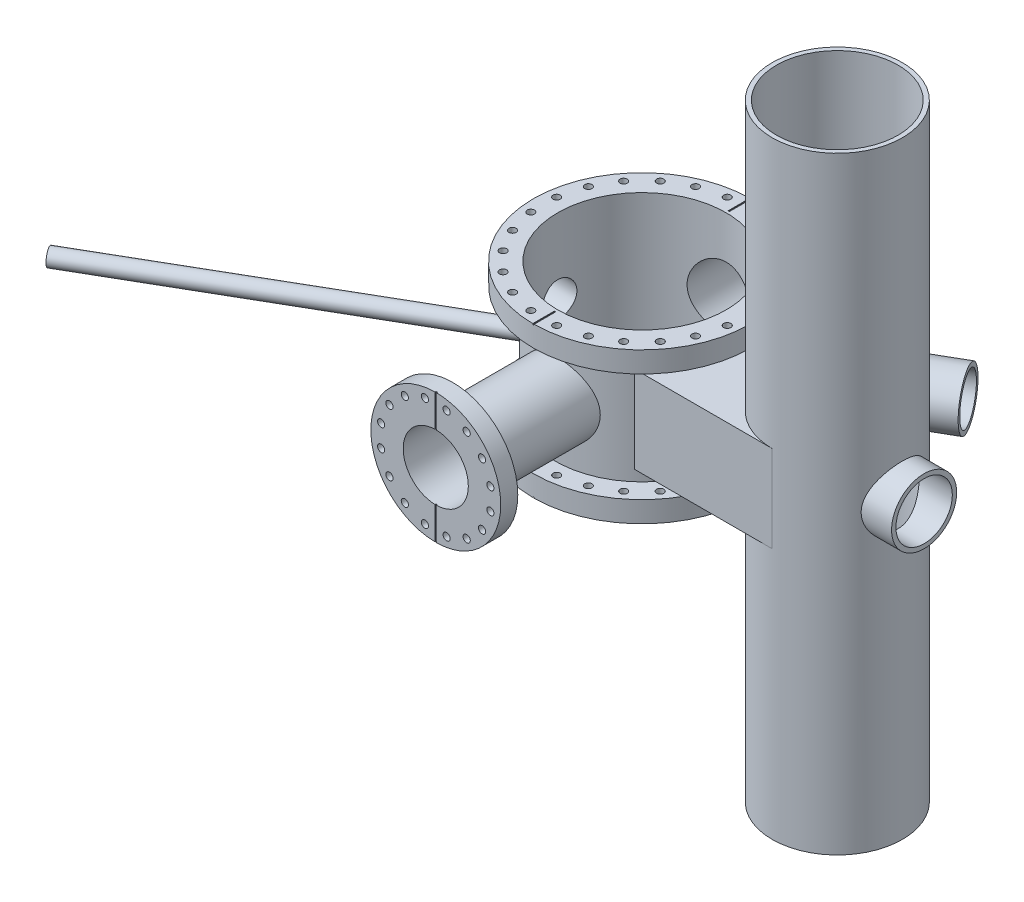
SolidWorks part; units mm, degrees
note: '?' marks a value the reader was unsure of.
ref_plane "Front Plane" through (0, 0, 0) normal (0, 0, 1) x (1, 0, 0)
ref_plane "Top Plane" through (0, 0, 0) normal (0, 1, 0) x (1, 0, 0)
ref_plane "Right Plane" through (0, 0, 0) normal (1, 0, 0) x (0, 0, -1)
sketch "Main_Chamber_Cylinder_Cross_Section" plane through (0, 0, 0) normal (0, 1, 0) x (1, 0, 0)
  circle A0 centre (0, 0) radius 98.552
  circle A1 centre (0, 0) radius 101.6
  dimension "main_chamber_ID_inches" = 197.104
  dimension "main_chamber_wall_thickness_inches" = 3.048
sketch "Main_Chamber_Cylinder_Height" plane through (0, 0, 0) normal (0, 0, 1) x (1, 0, 0)
  line L0 (0, -88.138) -> (0, 88.138) construction
  line L1 (101.6, 0) -> (-101.6, 0) construction
  line L2 (-47.8245, 0) -> (46.1077, 0) construction
  point P8 (0, 0)
  dimension "main_chamber_cyl_height_inches" = 176.276
extrude "Main_Chamber_Cylinder" add sketch "Main_Chamber_Cylinder_Cross_Section" along normal up to vertex (88.138 mm away) and the other way up to vertex (88.138 mm away) up to point (0, 88.138, 0)
sketch "Sketch1" plane through (0, 88.138, 0) normal (0, 1, 0) x (1, 0, 0)
  line L0 (0, 0) -> (0, 125.4308) construction
  point P0 (0, 0)
sketch "Sketch2" plane through (0, -88.138, 0) normal (0, -1, 0) x (1, 0, 0)
  line L0 (0, 0) -> (0, 116.7419) construction
  point P0 (0, 0)
sketch "Sketch21" plane through (0, -88.138, 0) normal (0, -1, 0) x (1, 0, 0)
  circle A0 centre (0, 0) radius 127
  circle A1 centre (0, 0) radius 101.6
  dimension "D1" = 203.2
  dimension "D2" = 254
extrude "Extrude2" add sketch "Sketch21" against normal blind 24.5
sketch "Sketch5" plane through (0, -88.138, 0) normal (0, -1, 0) x (1, 0, 0)
  line L0 (0, 0) -> (0, 210.1139) construction
  line L2 (0, -200000) -> (0, 200116.7419) construction
  line L3 (0, 0) -> (-224.4949, 0) construction
  line L4 (0.7938, 152.45) -> (-0.7938, 152.45)
  line L5 (-0.7938, 152.45) -> (-0.7937, 101.65)
  line L6 (-0.7937, 101.65) -> (0.7937, 101.65)
  line L7 (0.7938, 152.45) -> (0.7937, 101.65)
  line L8 (-0.7937, -101.65) -> (0.7937, -101.65)
  line L9 (0.7938, -152.45) -> (-0.7938, -152.45)
  line L10 (0.7938, -152.45) -> (0.7937, -101.65)
  line L11 (-0.7938, -152.45) -> (-0.7937, -101.65)
  point P13 (0, 101.65)
  point P14 (0, 152.45)
  dimension "D1" = 50.8
  dimension "D2" = 1.5875
  dimension "D3" = 101.65
extrude "Extrude3" cut sketch "Sketch5" against normal blind 1.016
hole_wizard "Hole5" positions "3DSketch5" profile "Sketch9" legacy end condition up to next
sketch3d "3DSketch5"
  line L0 (10.1144, -88.138, 76.8265) -> (0, -88.138, 0) construction
  line L2 (0, -88.138, 0) -> (0, -88.138, 116.7419) construction
  point P0 (15.1313, -88.138, 114.9338)
  dimension "D1" = 7.5
  dimension "D2" = 115.9256
sketch "Sketch9" plane through (15.1313, -88.138, 114.9338) normal (1, 0, 0) x (0, 0, -1)
  line L0 (0, 0) -> (0, 24.501)
  line L1 (0, 24.501) -> (4.2, 24.501)
  line L2 (4.2, 24.501) -> (4.2, 0)
  line L3 (4.2, 0) -> (0, 0)
  line L4 (0, 110) -> (0, -10) construction
  dimension "Diameter" = 8.4
  dimension "Depth" = 24.501
pattern_circular "CirPattern7" count 24 over 360 about axis through (0, 0, 0) along (0, 1, 0) of "Hole5"
other "OD10 Flange<1>"
sketch "Sketch22" plane through (0, 88.138, 0) normal (0, 1, 0) x (-1, 0, 0)
  circle A0 centre (0, 0) radius 127
  circle A1 centre (0, 0) radius 101.6
  dimension "D1" = 203.2
  dimension "D2" = 254
extrude "Extrude21" add sketch "Sketch22" against normal blind 24.5
sketch "Sketch51" plane through (0, 88.138, 0) normal (0, 1, 0) x (-1, 0, 0)
  line L0 (0, 0) -> (0, -210.1139) construction
  line L2 (0, 200000) -> (0, -200125.4308) construction
  line L3 (0, 0) -> (-224.4949, 0) construction
  line L4 (-0.7938, -152.45) -> (0.7938, -152.45)
  line L5 (0.7938, -152.45) -> (0.7937, -101.65)
  line L6 (0.7937, -101.65) -> (-0.7937, -101.65)
  line L7 (-0.7938, -152.45) -> (-0.7937, -101.65)
  line L8 (0.7937, 101.65) -> (-0.7937, 101.65)
  line L9 (-0.7938, 152.45) -> (0.7938, 152.45)
  line L10 (-0.7938, 152.45) -> (-0.7937, 101.65)
  line L11 (0.7938, 152.45) -> (0.7937, 101.65)
  point P13 (0, -101.65)
  point P14 (0, -152.45)
  dimension "D1" = 50.8
  dimension "D2" = 1.5875
  dimension "D3" = 101.65
extrude "Extrude31" cut sketch "Sketch51" against normal blind 1.016
hole_wizard "Hole51" positions "3DSketch51" profile "Sketch91" legacy end condition up to next
sketch3d "3DSketch51"
  line L0 (10.1144, 88.138, -76.8265) -> (0, 88.138, 0) construction
  line L2 (0, 88.138, 0) -> (0, 88.138, -125.4308) construction
  point P0 (15.1313, 88.138, -114.9338)
  dimension "D1" = 7.5
  dimension "D2" = 115.9256
sketch "Sketch91" plane through (15.1313, 88.138, -114.9338) normal (1, 0, 0) x (0, 0, 1)
  line L0 (0, 0) -> (0, 24.501)
  line L1 (0, 24.501) -> (4.2, 24.501)
  line L2 (4.2, 24.501) -> (4.2, 0)
  line L3 (4.2, 0) -> (0, 0)
  line L4 (0, 110) -> (0, -10) construction
  dimension "Diameter" = 8.4
  dimension "Depth" = 24.501
pattern_circular "CirPattern71" count 24 over 360 about axis through (0, 0, 0) along (0, 1, 0) of "Hole51"
other "OD10 Flange<2>"
ref_plane "Plane1" through (0, 0, 241.3) normal (0, 0, 1) x (1, 0, 0)
sketch "Sketch92" plane through (0, 0, 241.3) normal (0, 0, 1) x (1, 0, 0)
  circle A0 centre (0, 0) radius 38.1
  circle A1 centre (0, 0) radius 43.18
  dimension "D1" = 76.2
  dimension "D2" = 5.08
extrude "Extrude32" add sketch "Sketch92" against normal up to next
sketch "Sketch93" plane through (0, 0, 241.3) normal (0, 0, 1) x (1, 0, 0)
  circle A0 centre (0, 0) radius 38.1
  circle A1 centre (0, 0) radius 38.1 construction
extrude "Extrude33" cut sketch "Sketch93" against normal up to next
sketch "Sketch94" plane through (0, 0, 241.3) normal (0, 0, 1) x (1, 0, 0)
  line L0 (0, 0) -> (0, 109.8314)
  point P0 (0, 0)
sketch "Sketch23" plane through (0, 0, 241.3) normal (0, 0, 1) x (1, 0, 0)
  circle A0 centre (0, 0) radius 76
  circle A1 centre (0, 0) radius 38.1
  dimension "D1" = 152
  dimension "D2" = 76.2
extrude "Extrude22" add sketch "Sketch23" against normal blind 20
sketch "Sketch52" plane through (0, 0, 241.3) normal (0, 0, 1) x (1, 0, 0)
  line L0 (0, 200000) -> (0, 200210.1139) construction
  line L1 (0.7937, -76) -> (-0.7937, -76)
  line L2 (0, 0) -> (0, 109.8314) construction
  line L3 (0, 0) -> (-224.4949, 0) construction
  line L4 (0.7937, 76) -> (-0.7937, 76)
  line L5 (-0.7937, 76) -> (-0.7937, -76)
  line L7 (0.7937, 76) -> (0.7937, -76)
  point P4 (0, -76)
  point P8 (0, -47.1916)
  point P13 (0, 47.1916)
  point P14 (0, 76)
  point P15 (0.7937, 0)
  point P16 (-0.7937, 0)
  dimension "D1" = 152
  dimension "D2" = 1.5875
extrude "Extrude35" cut sketch "Sketch52" against normal blind 1.016
sketch "Sketch8" plane through (0, 0, 241.3) normal (0, 0, 1) x (1, 0, 0)
  line L0 (0, 0) -> (12.7101, 63.8982) construction
  line L1 (0, 0) -> (0, 109.8314) construction
  circle A0 centre (12.7101, 63.8982) radius 4.2
  dimension "D3" = 8.4
  dimension "D1" = 11.25
  dimension "D2" = 65.15
extrude "Extrude4" cut sketch "Sketch8" against normal up to next
pattern_circular "CirPattern1" count 16 over 360 about axis through (0, 0, 0) along (0, 0, 1) of "Extrude4"
other "OD6 Flange<1>"
mirror "Mirror2" about plane through (0, 0, 0) normal (0, 0, 1) of "Extrude33", "Extrude32"
sketch "Sketch95" plane through (0, 0, -241.3) normal (0, 0, -1) x (-1, 0, 0)
  line L0 (0, 0) -> (0, 109.8314)
  circle A0 centre (0, 0) radius 38.1 construction
  point P0 (0, 0)
sketch "Sketch24" plane through (0, 0, -241.3) normal (0, 0, -1) x (-1, 0, 0)
  circle A0 centre (0, 0) radius 76
  circle A1 centre (0, 0) radius 38.1
  dimension "D1" = 152
  dimension "D2" = 76.2
extrude "Extrude23" add sketch "Sketch24" against normal blind 20
sketch "Sketch53" plane through (0, 0, -241.3) normal (0, 0, -1) x (-1, 0, 0)
  line L0 (0, 200000) -> (0, 200210.1139) construction
  line L1 (0.7937, -76) -> (-0.7937, -76)
  line L2 (0, 0) -> (0, 109.8314) construction
  line L3 (0, 0) -> (-224.4949, 0) construction
  line L4 (0.7937, 76) -> (-0.7937, 76)
  line L5 (-0.7937, 76) -> (-0.7937, -76)
  line L7 (0.7937, 76) -> (0.7937, -76)
  point P4 (0, -76)
  point P8 (0, -47.1916)
  point P13 (0, 47.1916)
  point P14 (0, 76)
  point P15 (0.7937, 0)
  point P16 (-0.7937, 0)
  dimension "D1" = 152
  dimension "D2" = 1.5875
extrude "Extrude36" cut sketch "Sketch53" against normal blind 1.016
sketch "Sketch81" plane through (0, 0, -241.3) normal (0, 0, -1) x (-1, 0, 0)
  line L0 (0, 0) -> (12.7101, 63.8982) construction
  line L1 (0, 0) -> (0, 109.8314) construction
  circle A0 centre (12.7101, 63.8982) radius 4.2
  dimension "D3" = 8.4
  dimension "D1" = 11.25
  dimension "D2" = 65.15
extrude "Extrude41" cut sketch "Sketch81" against normal up to next
pattern_circular "CirPattern11" count 16 over 360 about axis through (0, 0, 0) along (0, 0, 1) of "Extrude41"
other "OD6 Flange<2>"
ref_plane "Plane2" through (228.6, 0, 0) normal (1, 0, 0) x (0, 0, -1)
sketch "Sketch96" plane through (228.6, 0, 0) normal (1, 0, 0) x (0, 0, -1)
  line L0 (0, 0) -> (0, 118.9491) construction
  line L1 (0, 0) -> (-139.2511, 0) construction
  line L2 (76.2, 50.8) -> (-76.2, 50.8)
  line L3 (-76.2, 50.8) -> (-76.2, -50.8)
  line L4 (76.2, 50.8) -> (76.2, -50.8)
  line L5 (76.2, -50.8) -> (-76.2, -50.8)
  point P9 (0, 50.8)
  point P10 (76.2, 0)
  point P11 (-76.2, 0)
  dimension "D1" = 101.6
  dimension "D2" = 152.4
extrude "Extrude42" add sketch "Sketch96" against normal up to next
ref_plane "Plane3" through (0, 365.76, 0) normal (0, 1, 0) x (-1, 0, 0)
sketch "Sketch98" plane through (0, 365.76, 0) normal (0, 1, 0) x (-1, 0, 0)
  line L0 (-228.6, -76.2) -> (-228.6, 76.2) construction
  circle A0 centre (-228.6, 0) radius 76.2
  point P0 (-228.6, 0)
extrude "Extrude44" add sketch "Sketch98" against normal blind 711.2
sketch "Sketch99" plane through (0, 365.76, 0) normal (0, 1, 0) x (1, 0, 0)
  circle A0 centre (228.6, 0) radius 71.12
  circle A1 centre (228.6, 0) radius 76.2 construction
  dimension "D1" = 5.08
extrude "Extrude45" cut sketch "Sketch99" against normal blind 711.2
sketch3d "3DSketch52"
  point P0 (228.6, 50.8, 76.2)
  point P1 (228.6, -50.8, 76.2)
  point P3 (228.6, 50.8, -76.2)
  point P5 (228.6, -50.8, -76.2)
sketch "Sketch106" plane through (228.6, 0, 0) normal (1, 0, 0) x (0, 0, -1)
  line L0 (-76.2, 50.8) -> (-76.2, -50.8) construction
  line L1 (-71.12, 45.72) -> (71.12, 45.72)
  line L2 (-71.12, 45.72) -> (-71.12, -45.72)
  line L3 (-71.12, -45.72) -> (71.12, -45.72)
  line L4 (71.12, 45.72) -> (71.12, -45.72)
  line L5 (76.2, -50.8) -> (76.2, 50.8) construction
  dimension "D1" = 5.08
  dimension "D2" = 5.08
  dimension "D3" = 5.08
  dimension "D4" = 5.08
extrude "Extrude50" cut sketch "Sketch106" against normal up to next
ref_plane "Plane4" through (330.2, 0, 0) normal (1, 0, 0) x (0, 0, -1)
sketch "Sketch100" plane through (330.2, 0, 0) normal (1, 0, 0) x (0, 0, -1)
  circle A0 centre (0, 0) radius 38.1
  dimension "D1" = 76.2
extrude "Extrude46" add sketch "Sketch100" against normal up to next
sketch "Sketch101" plane through (330.2, 0, 0) normal (1, 0, 0) x (0, 0, -1)
  circle A0 centre (0, 0) radius 33.02
  circle A1 centre (0, 0) radius 38.1 construction
  dimension "D1" = 5.08
extrude "Extrude47" cut sketch "Sketch101" against normal up to next
ref_plane "Plane5" through (-152.4, 0, 0) normal (1, 0, 0) x (0, 0, -1)
sketch "Sketch102" plane through (-152.4, 0, 0) normal (1, 0, 0) x (0, 0, -1)
  circle A0 centre (0, 0) radius 25.4
  dimension "D1" = 50.8
extrude "Extrude48" add sketch "Sketch102" along normal up to next
sketch "Sketch103" plane through (-152.4, 0, 0) normal (-1, 0, 0) x (0, 0, 1)
  circle A0 centre (0, 0) radius 20.32
  circle A1 centre (0, 0) radius 25.4 construction
  dimension "D1" = 5.08
extrude "Extrude49" cut sketch "Sketch103" against normal up to next
sketch "Sketch107" plane through (0, 0, 0) normal (0, 1, 0) x (1, 0, 0)
  line L0 (0, 0) -> (-262.8343, 0) construction
  line L1 (0, 0) -> (-231.4042, -133.6013) construction
  dimension "D1" = 30
ref_axis "Slower Axis" through (0, 0, 0) along (-0.866, 0, 0.5)?
ref_plane "Slower Plane" through (0, 0, 0) normal (-0.866, 0, 0.5) x (0.5, 0, 0.866)
ref_plane "Plane7" through (-439.9409, 0, 254) normal (-0.866, 0, 0.5) x (0.5, 0, 0.866)
sketch "Sketch108" plane through (-439.9409, 0, 254) normal (-0.866, 0, 0.5) x (0.5, 0, 0.866)
  circle A0 centre (0, 0) radius 9.525
  dimension "D1" = 19.05
extrude "Extrude51" add sketch "Sketch108" against normal up to next
sketch "Sketch109" plane through (-439.9409, 0, 254) normal (-0.866, 0, 0.5) x (0.5, 0, 0.866)
  circle A0 centre (0, 0) radius 8.636
  dimension "D1" = 17.272
extrude "Extrude52" cut sketch "Sketch109" against normal up to next
ref_plane "Plane8" through (241.9675, 0, -139.7) normal (-0.866, 0, 0.5) x (0.5, 0, 0.866)
sketch "Sketch110" plane through (241.9675, 0, -139.7) normal (-0.866, 0, 0.5) x (0.5, 0, 0.866)
  circle A0 centre (0, 0) radius 31.75
  dimension "D1" = 63.5
extrude "Extrude53" add sketch "Sketch110" along normal up to next
sketch "Sketch111" plane through (241.9675, 0, -139.7) normal (0.866, 0, -0.5) x (-0.5, 0, -0.866)
  circle A0 centre (0, 0) radius 26.67
  circle A1 centre (0, 0) radius 31.75 construction
  dimension "D1" = 5.08
extrude "Extrude54" cut sketch "Sketch111" against normal up to next
equation "\"main_chamber_ID_inches\"=7.76"
equation "\"main_chamber_wall_thickness_inches\"=.12"
equation "\"main_chamber_cyl_height_inches\"=6.94"
